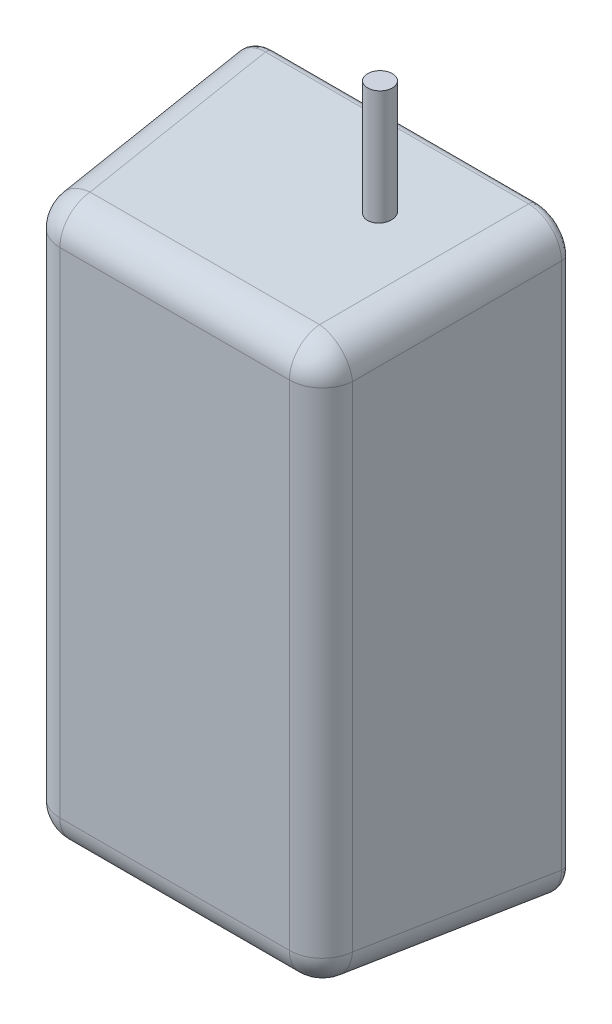
SolidWorks part; units mm, degrees
ref_plane "Front" through (0, 0, 0) normal (0, 0, 1) x (1, 0, 0)
ref_plane "Top" through (0, 0, 0) normal (0, 1, 0) x (1, 0, 0)
ref_plane "Right" through (0, 0, 0) normal (1, 0, 0) x (0, 0, -1)
sketch "Sketch1" plane through (0, 0, 0) normal (0, 0, 1) x (1, 0, 0)
  line L1 (-127, 228.6) -> (127, 228.6)
  line L2 (-127, 228.6) -> (-127, -228.6)
  line L3 (-127, -228.6) -> (127, -228.6)
  line L4 (127, 228.6) -> (127, -228.6)
  line L5 (-127, 228.6) -> (127, -228.6) construction
  line L6 (-127, -228.6) -> (127, 228.6) construction
  point P0 (0, 0)
  dimension "D1" = 254
  dimension "D2" = 457.2
extrude "Boss-Extrude1" add sketch "Sketch1" along normal blind 177.8 draft 5
fillet "Fillet1" radius 25.4 4 edges at (119.2223, -220.8223, 88.9) (-119.2223, -220.8223, 88.9) (119.2223, 220.8223, 88.9) (-119.2223, 220.8223, 88.9)
fillet "Fillet2" radius 25.4 8 edges at (-104.045, -205.645, 177.8) (-111.4445, 0, 177.8) (-104.045, 205.645, 177.8) (0, 213.0445, 177.8) (104.045, 205.645, 177.8) (111.4445, 0, 177.8) (104.045, -205.645, 177.8) (0, -213.0445, 177.8)
fillet "Fillet3" radius 6.35 8 edges at (119.6004, -221.2004, 0) (0, -228.6, 0) (-119.6004, -221.2004, 0) (-127, 0, 0) (-119.6004, 221.2004, 0) (0, 228.6, 0) (119.6004, 221.2004, 0) (127, 0, 0)
sketch "Sketch2" plane through (0, 0, 0) normal (0, 1, 0) x (1, 0, 0)
  line L0 (0, 0) -> (0, -69.85) construction
  line L1 (0, -69.85) -> (-76.2, -69.85) construction
  line L2 (0, -69.85) -> (25.4, -69.85) construction
  circle A0 centre (-76.2, -69.85) radius 3.175
  circle A1 centre (25.4, -69.85) radius 9.525
  dimension "D3" = 6.35
  dimension "D4" = 19.05
  dimension "D1" = 25.4
  dimension "D2" = 76.2
  dimension "D5" = 69.85
extrude "Boss-Extrude2" add sketch "Sketch2" against normal blind 279.4
sketch "Sketch3" plane through (0, 0, 0) normal (0, 1, 0) x (1, 0, 0)
  line L0 (0, 0) -> (0, -64.4508) construction
  line L1 (0, -64.4508) -> (44.45, -64.4508) construction
  circle A0 centre (44.45, -64.4508) radius 9.525
  dimension "D2" = 19.05
  dimension "D1" = 44.45
  dimension "D3" = 64.4508
extrude "Boss-Extrude3" add sketch "Sketch3" along normal blind 310.388
